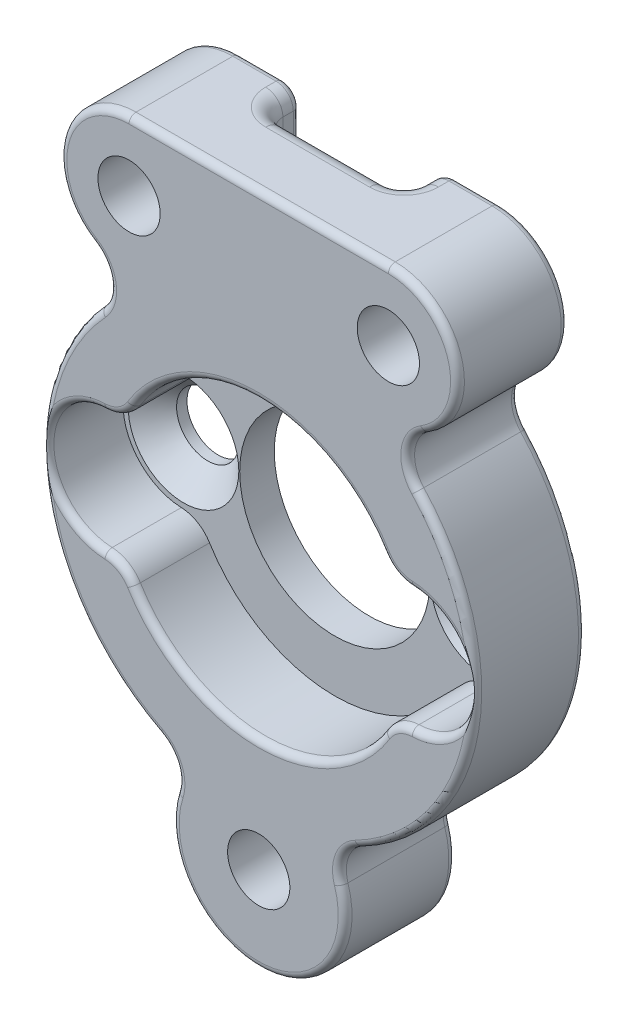
SolidWorks part; units mm, degrees
ref_plane "Front Plane" through (0, 0, 0) normal (0, 0, 1) x (1, 0, 0)
ref_plane "Top Plane" through (0, 0, 0) normal (0, 1, 0) x (1, 0, 0)
ref_plane "Right Plane" through (0, 0, 0) normal (1, 0, 0) x (0, 0, -1)
sketch "Sketch1" plane through (0, 0, 0) normal (0, 0, 1) x (1, 0, 0)
  line L0 (-11.1125, 0) -> (11.1125, 0) construction
  line L1 (0, 19.05) -> (0, -19.05) construction
  line L2 (-9.525, 19.05) -> (9.525, 19.05) construction
  line L3 (-9.525, 24.13) -> (9.525, 24.13)
  line L6 (-7.5402, 13.97) -> (-9.525, 13.97)
  line L7 (9.525, 13.97) -> (7.5402, 13.97)
  circle A0 centre (0, 0) radius 6.985
  arc A1 (-7.5402, 13.97) -> (-4.957, -15.0813) centre (0, 0) ccw
  circle A2 centre (-11.1125, 0) radius 2.286
  circle A3 centre (11.1125, 0) radius 2.286
  circle A7 centre (0, -19.05) radius 2.286
  arc A8 (4.957, -15.0812) -> (-4.957, -15.0813) centre (0, -19.05) cw
  arc A9 (4.957, -15.0812) -> (7.5402, 13.97) centre (0, 0) ccw
  arc A10 (-9.525, 24.13) -> (-9.525, 13.97) centre (-9.525, 19.05) ccw
  circle A12 centre (-9.525, 19.05) radius 2.286
  circle A13 centre (9.525, 19.05) radius 2.286
  arc A14 (9.525, 24.13) -> (9.525, 13.97) centre (9.525, 19.05) cw
  point P13 (0, 19.05)
  point P33 (4.957, -15.0812)
  dimension "D1" = 13.97
  dimension "D2" = 31.75
  dimension "D3" = 22.225
  dimension "D4" = 4.572
  dimension "D5" = 4.572
  dimension "D7" = 6.35
  dimension "D9" = 4.572
  dimension "D8" = 5.08
  dimension "D6" = 38.1
  dimension "D10" = 19.05
extrude "Boss-Extrude1" add sketch "Sketch1" along normal blind 8.128
sketch "Sketch2" plane through (0, 0, 8.128) normal (0, 0, 1) x (1, 0, 0)
  circle A2 centre (-11.1125, 0) radius 4.445
  circle A3 centre (11.1125, 0) radius 4.445
  dimension "D2" = 8.89
extrude "Cut-Extrude1" cut sketch "Sketch2" against normal offset from surface (5.588 mm away) 2.54 up to face at (-7.239, 19.05, 0)
sketch "Sketch3" plane through (0, 0, 8.128) normal (0, 0, 1) x (1, 0, 0)
  circle A0 centre (0, 0) radius 10.795
  dimension "D1" = 21.59
extrude "Cut-Extrude2" cut sketch "Sketch3" against normal offset from surface (5.588 mm away) 2.54 up to face at (-7.239, 19.05, 0)
fillet "Fillet1" radius 2.54 4 edges at (4.957, -15.0812, 4.064) (-4.957, -15.0812, 4.064) (7.5402, 13.97, 4.064) (-7.5402, 13.97, 4.064)
chamfer "Chamfer1" distance 1.778 angle 45 2 edges at (8.8265, 0, 2.54) (-13.3985, 0, 2.54)
fillet "Fillet2" radius 2.54 4 edges at (-9.9105, 4.2794, 5.334) (-9.9105, -4.2794, 5.334) (9.9105, -4.2794, 5.334) (9.9105, 4.2794, 5.334)
sketch "Sketch4" plane through (0, 0, 0) normal (0, 0, -1) x (-1, 0, 0)
  line L1 (-5.08, 25.4) -> (5.08, 25.4)
  line L2 (-5.08, 25.4) -> (-5.08, 12.7)
  line L3 (-5.08, 12.7) -> (5.08, 12.7)
  line L4 (5.08, 25.4) -> (5.08, 12.7)
  point P4 (0, 12.7)
  dimension "D1" = 12.7
  dimension "D2" = 10.16
  dimension "D3" = 12.7
extrude "Cut-Extrude3" cut sketch "Sketch4" against normal blind 2.54
fillet "Fillet4" radius 1.27 6 edges at (-5.08, 18.415, 2.54) (0, 12.7, 2.54) (5.08, 18.415, 2.54) (0, 24.13, 2.54) (-5.08, 24.13, 1.27) (5.08, 24.13, 1.27)
fillet "Fillet5" radius 0.508 33 edges at (14.4165, 20.421, 0) (10.9695, 12.8884, 0) (15.6411, -2.715, 0) (6.1233, -15.3804, 0) (0, -25.4, 0) (-6.1233, -15.3804, 0) (-15.6411, -2.715, 0) (-10.9695, 12.8884, 0) (-14.4165, 20.421, 0) (10.0827, 4.7862, 8.128) (15.5575, 0, 8.128) (10.0827, -4.7862, 8.128) (0, -10.795, 8.128) (-10.0827, -4.7862, 8.128) (-15.5575, 0, 8.128) (-10.0827, 4.7862, 8.128) (-10.9695, 12.8884, 8.128) (-14.4165, 20.421, 8.128) (0, 24.13, 8.128) (14.4165, 20.421, 8.128) (10.9695, 12.8884, 8.128) (15.6411, -2.715, 8.128) (6.1233, -15.3804, 8.128) (0, -25.4, 8.128) (-6.1233, -15.3804, 8.128) (-7.9375, 24.13, 0) (7.9375, 24.13, 0) (0, 10.795, 8.128) (-15.6411, -2.715, 8.128) (-5.08, 17.78, 0) (-5.452, 23.758, 0) (5.08, 17.78, 0) (5.452, 23.758, 0)
